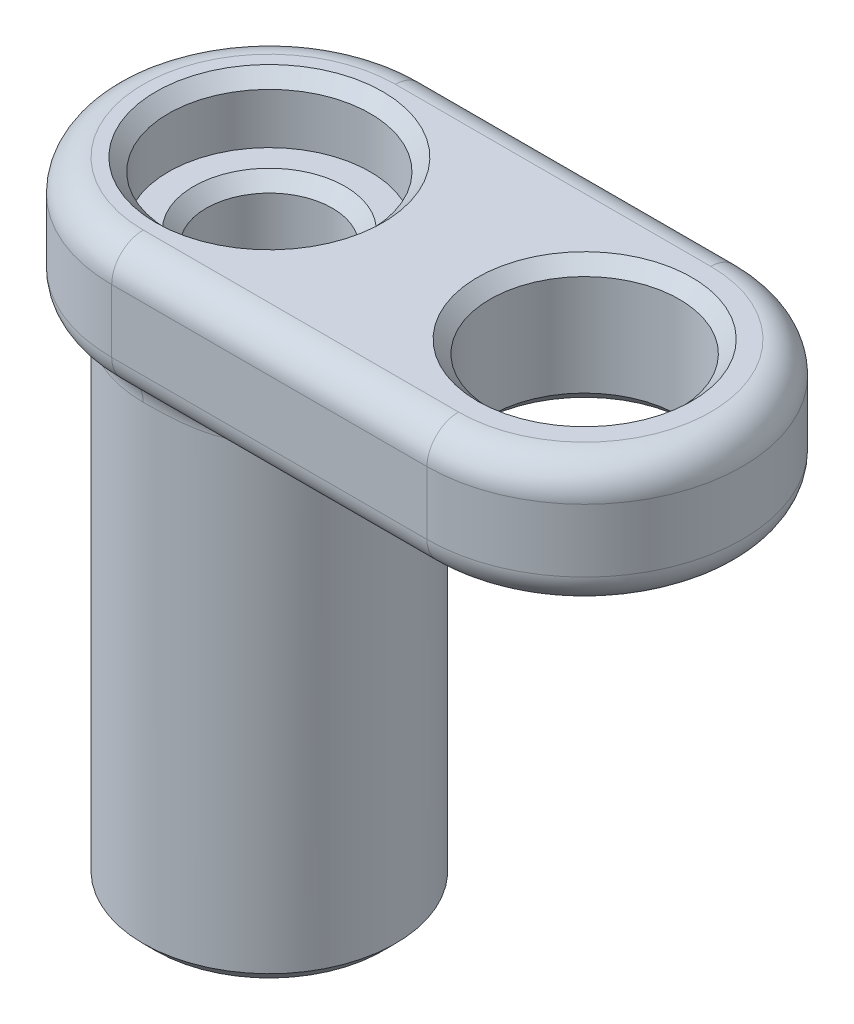
SolidWorks part; units mm, degrees
ref_plane "Front Plane" through (0, 0, 0) normal (0, 0, 1) x (1, 0, 0)
ref_plane "Top Plane" through (0, 0, 0) normal (0, 1, 0) x (1, 0, 0)
ref_plane "Right Plane" through (0, 0, 0) normal (1, 0, 0) x (0, 0, -1)
sketch "Sketch1" plane through (0, 0, 0) normal (0, 1, 0) x (1, 0, 0)
  circle A0 centre (0, 0) radius 20
  dimension "D1" = 40
extrude "Boss-Extrude1" add sketch "Sketch1" along normal blind 100
sketch "Sketch2" plane through (0, 100, 0) normal (0, 1, 0) x (1, 0, 0)
  line L0 (0, 0) -> (50, 0) construction
  line L1 (0, 25) -> (50, 25)
  line L2 (0, -25) -> (50, -25)
  arc A0 (0, 25) -> (0, -25) centre (0, 0) ccw
  arc A1 (50, -25) -> (50, 25) centre (50, 0) ccw
  point P3 (25, 0)
  dimension "D1" = 25
  dimension "D2" = 50
extrude "Boss-Extrude2" add sketch "Sketch2" against normal blind 20
sketch "Sketch5" plane through (0, 100, 0) normal (0, 1, 0) x (1, 0, 0)
  point P0 (0, 0)
hole_wizard "CBORE for M10 Hex Head Cap Screw1" positions "Sketch5" profile "Sketch6" counterbore size "M10" standard "ISO" end condition through all
sketch "Sketch6" plane through (0, 100, 0) normal (1, 0, 0) x (0, 0, 1)
  line L0 (0, 0) -> (0, 100)
  line L1 (0, 100) -> (10, 100)
  line L3 (10, 100) -> (10, 10)
  line L4 (10, 10) -> (16, 10)
  line L5 (16, 10) -> (16, 0)
  line L7 (16, 0) -> (0, 0)
  line L11 (0, -6.35) -> (0, 107.95) construction
  dimension "Thru Hole Dia." = 20
  dimension "Thru Hole Depth" = 100
  dimension "C'Bore Dia." = 32
  dimension "C'Bore Depth" = 10
sketch "Sketch7" plane through (0, 100, 0) normal (0, 1, 0) x (1, 0, 0)
  point P0 (50, 0)
hole_wizard "Ø1.0mm Dowel Hole1" positions "Sketch7" profile "Sketch8" hole size "Ø1.0" standard "ISO" end condition through all
sketch "Sketch8" plane through (50, 100, 0) normal (1, 0, 0) x (0, 0, 1)
  line L0 (0, 0) -> (0, 100)
  line L1 (0, 100) -> (15, 100)
  line L2 (15, 100) -> (15, 0)
  line L5 (15, 0) -> (0, 0)
  line L11 (0, -6.35) -> (0, 107.95) construction
  dimension "Thru Hole Dia." = 30
  dimension "Thru Hole Depth" = 100
chamfer "Chamfer1" distance 2 angle 45 6 edges at (0, 0, 10) (0, 0, 20) (50, 80, 15) (50, 100, 15) (0, 90, 10) (0, 100, 16)
fillet "Fillet2" radius 5 4 edges at (25, 80, 25) (-25, 80, 0) (25, 80, -25) (75, 80, 0)
fillet "Fillet3" radius 5 6 edges at (-20, 80, 0) (25, 100, 25) (-25, 100, 0) (25, 100, -25) (20, 80, 0) (75, 100, 0)
